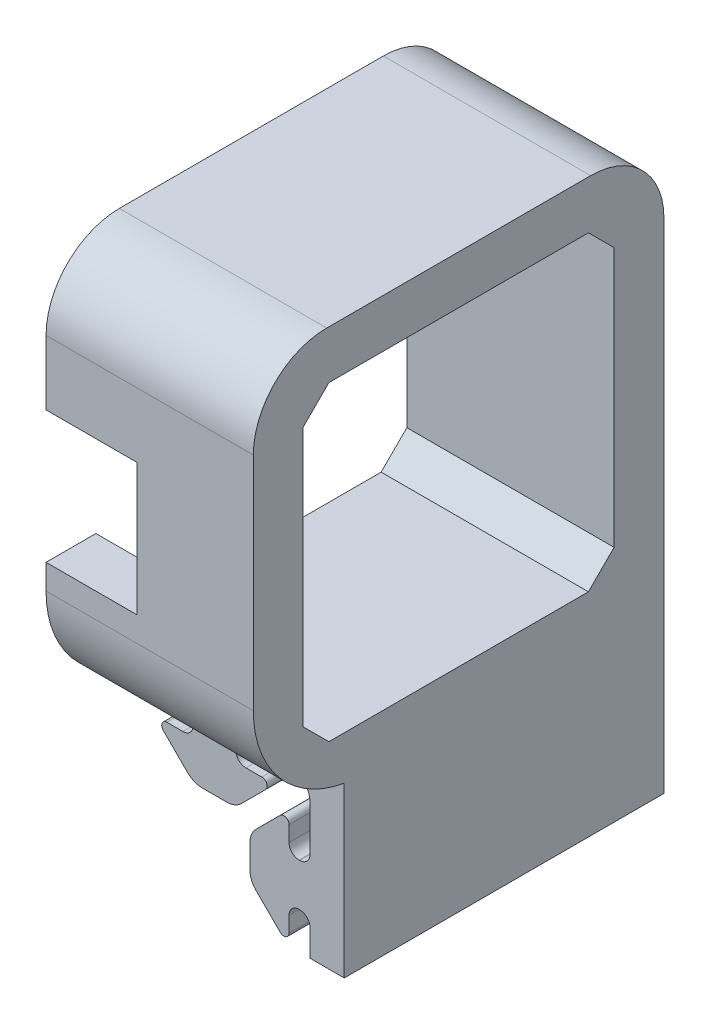
SolidWorks part; units mm, degrees
ref_plane "Front Plane" through (0, 0, 0) normal (0, 0, 1) x (1, 0, 0)
ref_plane "Top Plane" through (0, 0, 0) normal (0, 1, 0) x (1, 0, 0)
ref_plane "Right Plane" through (0, 0, 0) normal (1, 0, 0) x (0, 0, -1)
sketch "Sketch1" plane through (0, 0, 0) normal (0, 0, 1) x (1, 0, 0)
  line L0 (13.02, -7.9417) -> (17.7, -7.9417)
  line L1 (-10.5664, 13.02) -> (-10.5664, 70.02)
  line L2 (-10.5664, 70.02) -> (17.7, 70.02)
  line L3 (17.7, -7.9417) -> (17.7, 70.02)
  line L10 (12.7, -6.3331) -> (12.7, -7.9417) construction
  line L11 (13.02, -5.3171) -> (13.02, -4.2875)
  line L12 (11.651, -2.9185) -> (11.5392, -2.9185)
  line L13 (10.1702, -4.2875) -> (10.1702, -6.4021)
  line L14 (8.9631, -6.9029) -> (5.667, -3.6143)
  line L15 (4.8285, -1.5932) -> (4.8285, 1.5932)
  line L16 (5.667, 3.6143) -> (8.9631, 6.9029)
  line L17 (10.1702, 6.4021) -> (10.1702, 4.2875)
  line L18 (11.5392, 2.9185) -> (11.651, 2.9185)
  line L19 (13.02, 10.5773) -> (13.02, 4.2875)
  line L20 (6.3329, 13.02) -> (10.5626, 13.0198)
  line L22 (6.3329, 13.02) -> (4.2875, 13.02)
  line L23 (2.9185, 11.651) -> (2.9185, 11.5392)
  line L24 (4.2875, 10.1702) -> (6.4768, 10.1702)
  line L25 (6.981, 8.9509) -> (3.6723, 5.6497)
  line L26 (1.6558, 4.8158) -> (-1.6558, 4.8158)
  line L27 (-3.6723, 5.6497) -> (-6.981, 8.9509)
  line L28 (-6.4768, 10.1702) -> (-4.2875, 10.1702)
  line L29 (-2.9185, 11.5392) -> (-2.9185, 11.651)
  line L30 (-4.2875, 13.02) -> (-5.3171, 13.02)
  line L31 (-5.3171, 13.02) -> (-10.5664, 13.02)
  line L32 (13.02, -5.3171) -> (13.02, -7.9417)
  line L33 (13.02, -6.3331) -> (13.02, -7.9417) construction
  line L34 (13.02, 4.2875) -> (13.02, 5.3171) construction
  line L37 (5.3171, 13.02) -> (4.2875, 13.02) construction
  line L38 (-6.3331, 13.02) -> (-9.5504, 13.02) construction
  line L96 (12.7, -5.3171) -> (12.7, -4.2875) construction
  line L97 (11.651, -3.2385) -> (11.5392, -3.2385) construction
  line L98 (10.4902, -4.2875) -> (10.4902, -6.4021) construction
  line L99 (8.7371, -7.1294) -> (5.441, -3.8408) construction
  line L100 (4.5085, -1.5932) -> (4.5085, 1.5932) construction
  line L101 (5.441, 3.8408) -> (8.7371, 7.1294) construction
  line L102 (10.4902, 6.4021) -> (10.4902, 4.2875) construction
  line L103 (11.5392, 3.2385) -> (11.651, 3.2385) construction
  line L104 (12.7, 4.2875) -> (12.7, 5.3171) construction
  line L105 (12.7, 6.3331) -> (12.7, 9.5504) construction
  line L106 (9.5504, 12.7) -> (6.3331, 12.7) construction
  line L107 (5.3171, 12.7) -> (4.2875, 12.7) construction
  line L108 (3.2385, 11.651) -> (3.2385, 11.5392) construction
  line L109 (4.2875, 10.4902) -> (6.4768, 10.4902) construction
  line L110 (7.207, 8.7244) -> (3.8983, 5.4232) construction
  line L111 (1.6558, 4.4958) -> (-1.6558, 4.4958) construction
  line L112 (-3.8983, 5.4232) -> (-7.207, 8.7244) construction
  line L113 (-6.4768, 10.4902) -> (-4.2875, 10.4902) construction
  line L114 (-3.2385, 11.5392) -> (-3.2385, 11.651) construction
  line L115 (-4.2875, 12.7) -> (-5.3171, 12.7) construction
  line L116 (-6.3331, 12.7) -> (-9.5504, 12.7) construction
  arc A0 (13.02, -4.2875) -> (11.651, -2.9185) centre (11.651, -4.2875) ccw
  arc A1 (11.5392, -2.9185) -> (10.1702, -4.2875) centre (11.5392, -4.2875) ccw
  arc A2 (8.9631, -6.9029) -> (10.1702, -6.4021) centre (9.4628, -6.4021) ccw
  arc A3 (4.8285, -1.5932) -> (5.667, -3.6143) centre (7.6835, -1.5932) ccw
  arc A4 (5.667, 3.6143) -> (4.8285, 1.5932) centre (7.6835, 1.5932) ccw
  arc A5 (10.1702, 6.4021) -> (8.9631, 6.9029) centre (9.4628, 6.4021) ccw
  arc A6 (10.1702, 4.2875) -> (11.5392, 2.9185) centre (11.5392, 4.2875) ccw
  arc A7 (11.651, 2.9185) -> (13.02, 4.2875) centre (11.651, 4.2875) ccw
  arc A8 (4.2875, 13.02) -> (2.9185, 11.651) centre (4.2875, 11.651) ccw
  arc A9 (2.9185, 11.5392) -> (4.2875, 10.1702) centre (4.2875, 11.5392) ccw
  arc A10 (6.981, 8.9509) -> (6.4768, 10.1702) centre (6.4768, 9.4563) ccw
  arc A11 (1.6558, 4.8158) -> (3.6723, 5.6497) centre (1.6558, 7.6708) ccw
  arc A12 (-3.6723, 5.6497) -> (-1.6558, 4.8158) centre (-1.6558, 7.6708) ccw
  arc A13 (-6.4768, 10.1702) -> (-6.981, 8.9509) centre (-6.4768, 9.4563) ccw
  arc A14 (-4.2875, 10.1702) -> (-2.9185, 11.5392) centre (-4.2875, 11.5392) ccw
  arc A15 (-2.9185, 11.651) -> (-4.2875, 13.02) centre (-4.2875, 11.651) ccw
  arc A16 (13.02, 10.5773) -> (10.5626, 13.0198) centre (10.5918, 10.5918) ccw
  arc A17 (13.0198, 10.5625) -> (10.5626, 13.0198) centre (10.5918, 10.5918) ccw construction
  arc A114 (12.7, -5.3171) -> (12.7, -6.3331) centre (12.7, -5.8251) ccw construction
  arc A115 (12.7, -4.2875) -> (11.651, -3.2385) centre (11.651, -4.2875) ccw construction
  arc A116 (11.5392, -3.2385) -> (10.4902, -4.2875) centre (11.5392, -4.2875) ccw construction
  arc A117 (8.7371, -7.1294) -> (10.4902, -6.4021) centre (9.4628, -6.4021) ccw construction
  arc A118 (4.5085, -1.5932) -> (5.441, -3.8408) centre (7.6835, -1.5932) ccw construction
  arc A119 (5.441, 3.8408) -> (4.5085, 1.5932) centre (7.6835, 1.5932) ccw construction
  arc A120 (10.4902, 6.4021) -> (8.7371, 7.1294) centre (9.4628, 6.4021) ccw construction
  arc A121 (10.4902, 4.2875) -> (11.5392, 3.2385) centre (11.5392, 4.2875) ccw construction
  arc A122 (11.651, 3.2385) -> (12.7, 4.2875) centre (11.651, 4.2875) ccw construction
  arc A123 (12.7, 6.3331) -> (12.7, 5.3171) centre (12.7, 5.8251) ccw construction
  arc A124 (12.6998, 10.5664) -> (12.7, 9.5504) centre (12.7, 10.0584) ccw construction
  arc A125 (12.6998, 10.5664) -> (10.5664, 12.6998) centre (10.5918, 10.5918) ccw construction
  arc A126 (9.5504, 12.7) -> (10.5664, 12.6998) centre (10.0584, 12.7) ccw construction
  arc A127 (5.3171, 12.7) -> (6.3331, 12.7) centre (5.8251, 12.7) ccw construction
  arc A128 (4.2875, 12.7) -> (3.2385, 11.651) centre (4.2875, 11.651) ccw construction
  arc A129 (3.2385, 11.5392) -> (4.2875, 10.4902) centre (4.2875, 11.5392) ccw construction
  arc A130 (7.207, 8.7244) -> (6.4768, 10.4902) centre (6.4768, 9.4563) ccw construction
  arc A131 (1.6558, 4.4958) -> (3.8983, 5.4232) centre (1.6558, 7.6708) ccw construction
  arc A132 (-3.8983, 5.4232) -> (-1.6558, 4.4958) centre (-1.6558, 7.6708) ccw construction
  arc A133 (-6.4768, 10.4902) -> (-7.207, 8.7244) centre (-6.4768, 9.4563) ccw construction
  arc A134 (-4.2875, 10.4902) -> (-3.2385, 11.5392) centre (-4.2875, 11.5392) ccw construction
  arc A135 (-3.2385, 11.651) -> (-4.2875, 12.7) centre (-4.2875, 11.651) ccw construction
  arc A136 (-6.3331, 12.7) -> (-5.3171, 12.7) centre (-5.8251, 12.7) ccw construction
  arc A137 (-10.5664, 12.6998) -> (-9.5504, 12.7) centre (-10.0584, 12.7) ccw construction
  dimension "D1" = 57
  dimension "D6" = 5
  dimension "D8" = 0.32
  dimension "D7" = 6.2898
  dimension "D9" = 4.2297
extrude "Boss-Extrude1" add sketch "Sketch1" along normal blind 56 contours L3 L2 L1 L31 L30 A15 L29 A14 L28 A13 L27 A12 L26 A11 L25 A10 L24 A9 L23 A8 L22 L20 A16 L19 A7 L18 A6 L17 A5 L16 A4 L15 A3 L14 A2 L13 A1 L12 A0 L11 L32 L0
sketch "Sketch14" plane through (17.7, 0, 0) normal (1, 0, 0) x (0, 0, -1)
  line L4 (-56, -7.9417) -> (-56, 70.02) construction
  line L5 (0, -7.9417) -> (0, 70.02) construction
  line L6 (-56, 70.02) -> (0, 70.02) construction
  line L11 (0, 21.02) -> (-56, 21.02) construction
  line L12 (-28, 70.02) -> (-28, 21.02) construction
  line L14 (-49.2, 21.02) -> (-6.8, 21.02)
  line L15 (-49.2, 21.02) -> (-49.2, 63.42)
  line L16 (-49.2, 63.42) -> (-6.8, 63.42)
  line L17 (-6.8, 21.02) -> (-6.8, 63.42)
  point P14 (-28, 63.42)
  dimension "D1" = 42.4
  dimension "D2" = 42.4
other "AlignGroup1"
extrude "Cut-Extrude1" cut sketch "Sketch14" against normal blind 56
chamfer "Chamfer1" distance 3.5 4 edges at (3.5668, 21.02, 6.8) (3.5668, 21.02, 49.2) (3.5668, 63.42, 6.8) (3.5668, 63.42, 49.2)
fillet "Fillet1" radius 10 2 edges at (3.5668, 70.02, 56) (3.5668, 70.02, 0)
sketch "Sketch16" plane through (17.7, 0, 0) normal (1, 0, 0) x (0, 0, -1)
  line L1 (-56, -7.9417) -> (-43.6, -7.9417)
  line L2 (-56, -7.9417) -> (-56, 15.0583)
  line L3 (-56, 15.0583) -> (-43.6, 15.0583)
  line L4 (-43.6, -7.9417) -> (-43.6, 15.0583)
  dimension "D1" = 23
  dimension "D2" = 12.4
extrude "Cut-Extrude3" cut sketch "Sketch16" against normal through all
sketch "Sketch17" plane through (0, 0, 56) normal (0, 0, 1) x (1, 0, 0)
  line L0 (17.7, 42.22) -> (-10.5664, 42.22) construction
  line L2 (-13.62, 51.22) -> (1.8336, 51.22)
  line L3 (-13.62, 51.22) -> (-13.62, 33.22)
  line L4 (17.7, 24.52) -> (17.7, 59.92)
  line L5 (-10.5664, 24.52) -> (17.7, 24.52)
  line L6 (-10.5664, 59.92) -> (-10.5664, 24.52)
  line L7 (17.7, 59.92) -> (-10.5664, 59.92)
  line L8 (17.7, 24.52) -> (17.7, 59.92) construction
  line L9 (-10.5664, 24.52) -> (17.7, 24.52) construction
  line L10 (-10.5664, 59.92) -> (-10.5664, 24.52) construction
  line L11 (17.7, 59.92) -> (-10.5664, 59.92) construction
  line L12 (-13.62, 33.22) -> (1.8336, 33.22)
  line L13 (1.8336, 51.22) -> (1.8336, 33.22)
  point P10 (1.8336, 42.22)
  dimension "D2" = 18
  dimension "D3" = 12.4
  dimension "D1" = 0
extrude "Cut-Extrude4" cut sketch "Sketch17" against normal up to next
fillet "Fillet4" radius 15 1 edges at (3.5668, 15.0583, 56)
